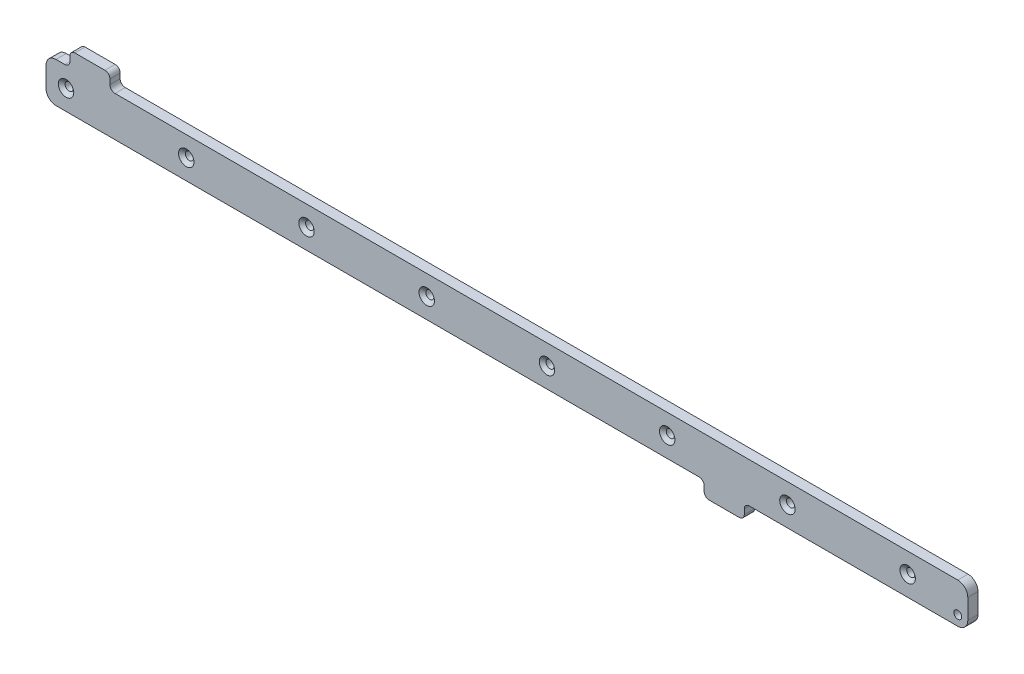
SolidWorks part; units mm, degrees
material "PC High Viscosity"
ref_plane "Front Plane" through (0, 0, 0) normal (0, 0, 1) x (1, 0, 0)
ref_plane "Top Plane" through (0, 0, 0) normal (0, 1, 0) x (1, 0, 0)
ref_plane "Right Plane" through (0, 0, 0) normal (1, 0, 0) x (0, 0, -1)
sketch "Sketch1" plane through (0, 0, 0) normal (0, 0, 1) x (1, 0, 0)
  line L1 (0, 0) -> (40.5308, 0)
  line L2 (0, 0) -> (0, 25.4)
  line L3 (0, 25.4) -> (15.1308, 25.4)
  line L4 (584.2, 0) -> (584.2, 25.4)
  line L5 (15.1308, 34.925) -> (40.5308, 34.925)
  line L6 (40.5308, 34.925) -> (40.5308, 25.4)
  line L7 (15.1308, 34.925) -> (15.1308, 25.4)
  line L11 (584.2, 10.0162) -> (577.85, 13.6823) construction
  line L12 (577.85, 13.6823) -> (571.5, 10.0162) construction
  line L13 (571.5, 10.0162) -> (571.5, 2.6838) construction
  line L14 (571.5, 2.6838) -> (577.85, -0.9823) construction
  line L15 (577.85, -0.9823) -> (584.2, 2.6838) construction
  line L16 (584.2, 2.6838) -> (584.2, 10.0162) construction
  line L19 (40.5308, 25.4) -> (584.2, 25.4)
  line L20 (40.5308, 0) -> (417.1409, 0)
  line L21 (442.5409, 0) -> (442.5409, -9.525)
  line L22 (442.5409, -9.525) -> (417.1409, -9.525)
  line L23 (417.1409, -9.525) -> (417.1409, 0)
  line L24 (442.5409, 0) -> (584.2, 0)
  circle A0 centre (577.85, 6.35) radius 2.4892
  circle A1 centre (577.85, 6.35) radius 6.35 construction
  dimension "D5" = 4.9784
  dimension "D6" = 9.525
  dimension "D7" = 12.7
  dimension "D1" = 584.2
  dimension "D2" = 25.4
  dimension "D3" = 25.4
  dimension "D4" = 40.5308
  dimension "D10" = 167.0591
extrude "Boss-Extrude1" add sketch "Sketch1" along normal blind 6.477 contours L6 L5 L3 | L1 L4 L3 L2 A0 | L1 region at (289.7362, 12.7081, 0)
fillet "Fillet2" radius 6.35 4 edges at (0, 0, 3.2385) (0, 25.4, 3.2385) (584.2, 0, 3.2385) (584.2, 25.4, 3.2385)
sketch "Sketch2" plane through (0, 0, 6.477) normal (0, 0, 1) x (1, 0, 0)
  line L0 (6.35, 25.4) -> (15.1308, 25.4) construction
  line L1 (584.2, 19.05) -> (584.2, 6.35) construction
  circle A0 centre (546.1, 12.7) radius 2.0193
  dimension "D1" = 4.0386
  dimension "D2" = 12.7
  dimension "D3" = 38.1
hole_wizard "CSK for #10 Flat Head Machine Screw (100)1" positions "Sketch4" profile "Sketch5" countersink size "#10" standard "ANSI Inch" end condition through all
sketch "Sketch4" plane through (0, 0, 6.477) normal (0, 0, 1) x (1, 0, 0)
  line L0 (584.2, 12.7) -> (0, 12.7) construction
  line L1 (584.2, 19.05) -> (584.2, 6.35) construction
  line L2 (0, 6.35) -> (0, 19.05) construction
  line L3 (6.35, 25.4) -> (15.1308, 25.4) construction
  point P11 (546.1, 12.7)
  dimension "D1" = 12.7
  dimension "D2" = 38.1
sketch "Sketch5" plane through (546.1, 12.7, 6.477) normal (1, 0, 0) x (0, -1, 0)
  line L0 (0, 0) -> (0, 6.477)
  line L1 (0, 6.477) -> (2.5527, 6.477)
  line L2 (2.5527, 6.477) -> (2.5527, 1.9608)
  line L3 (2.5527, 1.9608) -> (4.8895, 0)
  line L5 (4.8895, 0) -> (0, 0)
  line L6 (-2.5527, 1.9608) -> (-4.8895, 0) construction
  line L11 (0, -6.35) -> (0, 107.95) construction
  dimension "Thru Hole Dia." = 5.1054
  dimension "Thru Hole Depth" = 6.477
  dimension "Near C'Sink Dia." = 9.779
  dimension "Near C'Sink Angle" = 100
pattern_linear "LPattern1" count 8 spacing 76.2 along (-1, 0, 0) of "CSK for #10 Flat Head Machine Screw (100)1"
fillet "Fillet3" radius 3.175 8 edges at (15.1308, 25.4, 3.2385) (15.1308, 34.925, 3.2385) (40.5308, 34.925, 3.2385) (40.5308, 25.4, 3.2385) (417.1409, 0, 3.2385) (417.1409, -9.525, 3.2385) (442.5409, -9.525, 3.2385) (442.5409, 0, 3.2385)
